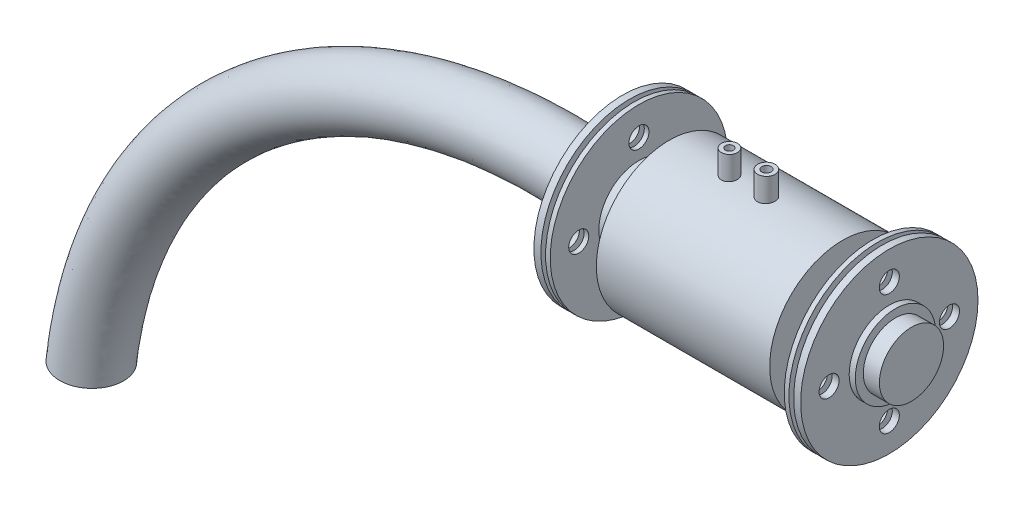
SolidWorks part; units mm, degrees
ref_plane "Front Plane" through (0, 0, 0) normal (0, 0, 1) x (1, 0, 0)
ref_plane "Top Plane" through (0, 0, 0) normal (0, 1, 0) x (1, 0, 0)
ref_plane "Right Plane" through (0, 0, 0) normal (1, 0, 0) x (0, 0, -1)
sketch "Sketch1" plane through (0, 0, 0) normal (0, 0, 1) x (1, 0, 0)
  line L0 (0, 0) -> (114.6182, 0)
  line L1 (114.6182, 0) -> (114.6182, 44.2182)
  line L2 (114.6182, 44.2182) -> (116.9455, 44.2182)
  line L3 (116.9455, 44.2182) -> (116.9455, 0.3012)
  line L4 (116.9455, 0.3012) -> (119.2727, 0.3012)
  line L5 (119.2727, 0.3012) -> (119.2727, 44.2182)
  line L6 (119.2727, 44.2182) -> (122.7636, 44.2182)
  line L7 (122.7636, 44.2182) -> (122.7636, 16)
  line L8 (122.7636, 16) -> (133.8182, 16)
  line L9 (133.8182, 16) -> (133.8182, 0)
  line L10 (81.4545, 0) -> (81.4545, 71.2727) construction
  line L11 (99.4909, 0) -> (99.4909, 36.3636)
  line L12 (99.4909, 36.3636) -> (13.0909, 36.3636)
  line L13 (13.0909, 36.3636) -> (13.0909, 0)
  line L14 (56.2909, 36.3636) -> (56.2909, -54.4) construction
  line L15 (0, 0) -> (-69.8182, 0)
  line L16 (-21.2364, 16) -> (-21.2364, 0)
  line L17 (-6.6909, 0.3012) -> (-6.6909, 44.2182)
  line L18 (-4.3636, 0.3012) -> (-6.6909, 0.3012)
  line L19 (-4.3636, 44.2182) -> (-4.3636, 0.3012)
  line L20 (-2.0364, 0) -> (-2.0364, 44.2182)
  line L21 (-10.1818, 16) -> (-21.2364, 16)
  line L22 (-10.1818, 44.2182) -> (-10.1818, 16)
  line L23 (-6.6909, 44.2182) -> (-10.1818, 44.2182)
  line L24 (-2.0364, 44.2182) -> (-4.3636, 44.2182)
  line L25 (-4.3636, 16) -> (13.0909, 16)
  line L26 (99.4909, 16) -> (114.6182, 16)
  line L27 (114.6182, 0) -> (133.8182, 0)
  line L28 (133.8182, 0) -> (114.6182, 0)
  dimension "D1" = 16
revolve "Revolve2" add sketch "Sketch1" angle 360 about L15 region at (5.5273, 8, 0) region at (56.2909, 18.1818, 0) region at (-11.3871, 13.8845, 0) region at (107.0545, 8, 0) region at (-3.2, 30.1091, 0) region at (122.7325, 16.3348, 0)
sketch "Sketch2" plane through (0, 0, 0) normal (0, 1, 0) x (1, 0, 0)
  circle A0 centre (43.0835, 0) radius 3.997
  circle A1 centre (61.5044, 0) radius 4.3445
extrude "Boss-Extrude1" add sketch "Sketch2" along normal blind 48
sketch "Sketch3" plane through (0, 48, 0) normal (0, 1, 0) x (1, 0, 0)
  circle A0 centre (43.0835, 0) radius 3.997 construction
  circle A1 centre (61.5044, 0) radius 4.3445 construction
  circle A2 centre (43.0835, 0) radius 3.997
  circle A3 centre (61.5044, 0) radius 4.3445
  circle A4 centre (61.5044, 0) radius 2.3445
  circle A5 centre (43.0835, 0) radius 1.997
  dimension "D1" = 2
extrude "Cut-Extrude1" cut sketch "Sketch3" against normal blind 48 contours A4 | A5
sketch "Sketch4" plane through (0, 0, 0) normal (1, 0, 0) x (0, 0, -1)
  line L0 (0, 0) -> (0, 50.979) construction
  line L1 (0, 0) -> (72.0939, 0) construction
  circle A0 centre (0, 30) radius 5
  circle A1 centre (30, 0) radius 5
  circle A2 centre (0, -30) radius 5
  circle A3 centre (-30, 0) radius 5
  point P15 (0, 0)
  dimension "D1" = 30
  dimension "D3" = 10
  dimension "D2" = 4
extrude "Cut-Extrude2" cut sketch "Sketch4" against normal blind 19
extrude "Cut-Extrude3" cut sketch "Sketch4<2>" along normal blind 19 from offset 110
sketch "Sketch4<2>" plane through (0, 0, 0) normal (1, 0, 0) x (0, 0, -1) same geometry as "Sketch4"
sketch "Sketch5" plane through (-10.1818, 0, 0) normal (-1, 0, 0) x (0, 0, 1)
  circle A0 centre (0, 0) radius 20
extrude "Boss-Extrude2" add sketch "Sketch5" along normal blind 4 and the other way blind 136
sketch "Sketch6" plane through (-21.2364, 0, 0) normal (-1, 0, 0) x (0, 0, 1)
  circle A1 centre (0, 0) radius 16
  circle A2 centre (0, 0) radius 16
  dimension "D1" = 0
sketch "Sketch7" plane through (0, 0, 0) normal (0, 0, 1) x (1, 0, 0)
  arc A0 (-21.2364, 0) -> (-274.9968, -203.3598) centre (-44.6263, -230.8192) ccw construction
  arc A1 (-21.2364, 0) -> (-274.9968, -203.3598) centre (-44.6263, -230.8192) ccw
sweep "Sweep1" add profiles "Sketch6" path "Sketch7"
